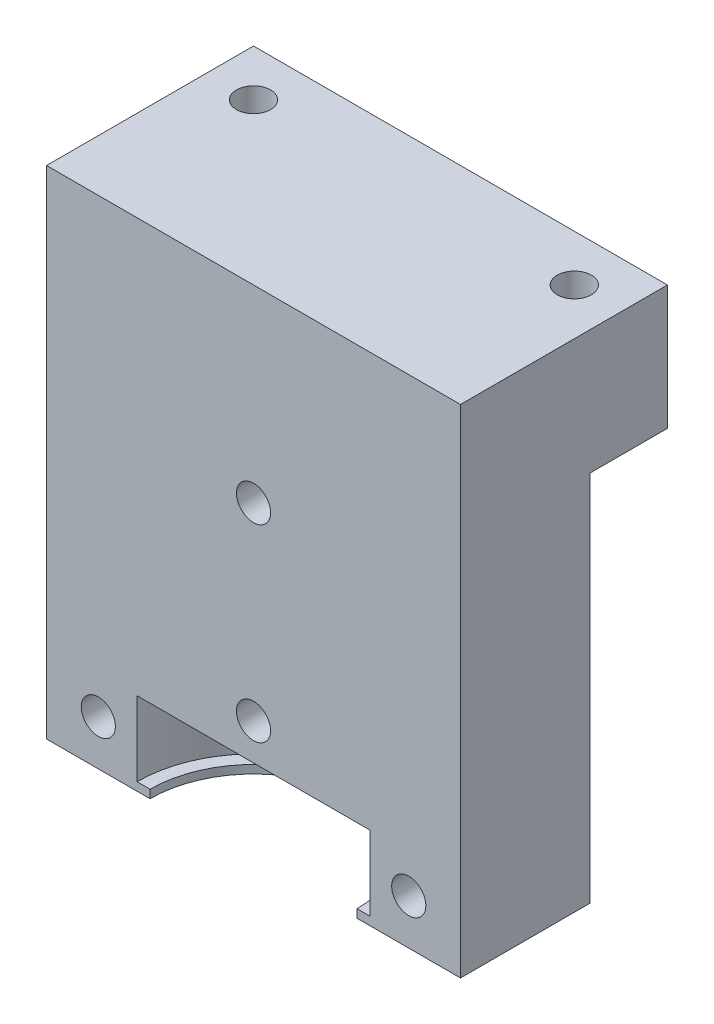
SolidWorks part; units mm, degrees
ref_plane "Front Plane" through (0, 0, 0) normal (0, 0, 1) x (1, 0, 0)
ref_plane "Top Plane" through (0, 0, 0) normal (0, 1, 0) x (1, 0, 0)
ref_plane "Right Plane" through (0, 0, 0) normal (1, 0, 0) x (0, 0, -1)
sketch "Sketch1" plane through (0, 0, 0) normal (0, 1, 0) x (1, 0, 0)
  line L1 (20, 20) -> (-20, 20)
  line L2 (20, 20) -> (20, -20)
  line L3 (20, -20) -> (-20, -20)
  line L4 (-20, 20) -> (-20, -20)
  line L5 (0, -20) -> (0, 20) construction
  line L6 (20, 0) -> (-20, 0) construction
  point P0 (0, 0)
extrude "Boss-Extrude1" add sketch "Sketch1" against normal blind 48
hole_wizard "M4x0.7 Tapped Hole1" positions "Sketch2" profile "Sketch3" tap size "M4x0.7" standard "ANSI Metric" end condition through all
sketch "Sketch2" plane through (0, 0, 0) normal (0, 1, 0) x (1, 0, 0)
  line L1 (-15.5, -15.5) -> (15.5, -15.5)
  line L2 (-15.5, -15.5) -> (-15.5, 15.5)
  line L3 (-15.5, 15.5) -> (15.5, 15.5)
  line L4 (15.5, -15.5) -> (15.5, 15.5)
  line L5 (15.5, 0) -> (0, 0) construction
  line L6 (0, 0) -> (0, -15.5) construction
  point P2 (-15.5, 15.5)
  point P4 (15.5, 15.5)
  point P6 (15.5, -15.5)
  point P8 (-15.5, -15.5)
  point P130 (-15.5, 15.5)
  point P131 (15.5, -15.5)
  point P132 (0, 0)
  dimension "D1" = 31
  dimension "D2" = 31
sketch "Sketch3" plane through (-15.5, 0, -15.5) normal (1, 0, 0) x (0, 0, 1)
  line L0 (0, 0) -> (0, 48)
  line L1 (0, 48) -> (1.65, 48)
  line L2 (1.65, 48) -> (1.65, 0)
  line L5 (1.65, 0) -> (0, 0)
  line L11 (0, -6.35) -> (0, 107.95) construction
  dimension "Thread Major Dia." = 3.3
  dimension "Thru Tap Drill Depth" = 48
sketch "Sketch10" plane through (0, 0, 0) normal (0, 1, 0) x (1, 0, 0)
  line L0 (20, -20) -> (20, 20) construction
  line L1 (-20, -20) -> (20, -20)
  line L2 (-20, -20) -> (-20, 0)
  line L3 (-20, 0) -> (20, 0)
  line L4 (20, -20) -> (20, 0)
extrude "Cut-Extrude4" cut sketch "Sketch10" against normal through all
sketch "Sketch11" plane through (0, 0, 0) normal (0, 0, 1) x (1, 0, 0)
  line L0 (0, 0) -> (0, -40) construction
  line L1 (0, -40) -> (11.25, -40)
  line L2 (0, -40) -> (0, -47.2)
  line L3 (0, -47.2) -> (11.25, -47.2)
  line L4 (11.25, -40) -> (11.25, -47.2)
  line L5 (20, 0) -> (-20, 0) construction
  dimension "D1" = 40
  dimension "D2" = 7.2
  dimension "D3" = 22.5
revolve "Cut-Revolve2" cut sketch "Sketch11" angle 360 about L0
sketch "Sketch12" plane through (0, -48, 0) normal (0, -1, 0) x (1, 0, 0)
  line L0 (20, 0) -> (-20, 0) construction
  circle A0 centre (0, 0) radius 10
  dimension "D1" = 20
extrude "Cut-Extrude5" cut sketch "Sketch12" against normal up to next
hole_wizard "M4x0.7 Tapped Hole2" positions "Sketch13" profile "Sketch14" tap size "M4x0.7" standard "ANSI Metric" end condition through all
sketch "Sketch13" plane through (0, 0, -20) normal (0, 0, -1) x (-1, 0, 0)
  line L0 (-15, -43.6281) -> (15, -43.6281) construction
  line L3 (0, -43.6281) -> (0, -36.4844) construction
  line L4 (0, -36.4844) -> (0, -18.2422) construction
  line L5 (0, -18.2422) -> (0, 0) construction
  line L8 (10, -47.2) -> (-10, -47.2) construction
  point P8 (15, -43.6281)
  point P10 (-15, -43.6281)
  point P12 (0, -36.4844)
  point P14 (0, -18.2422)
  point P33 (0, 0)
  dimension "D1" = 30
  dimension "D2" = 3.5719
  dimension "D3" = 7.1437
sketch "Sketch14" plane through (-15, -43.6281, -20) normal (1, 0, 0) x (0, 1, 0)
  line L0 (0, 0) -> (0, 20)
  line L1 (0, 20) -> (1.65, 20)
  line L2 (1.65, 20) -> (1.65, 0)
  line L5 (1.65, 0) -> (0, 0)
  line L11 (0, -6.35) -> (0, 107.95) construction
  dimension "Thru Tap Drill Dia." = 3.3
  dimension "Thru Tap Drill Depth" = 20
cosmetic thread "Hole Thread1" parameters "D2"=4
cosmetic thread "Hole Thread2" parameters "D2"=4
cosmetic thread "Hole Thread3" parameters "D2"=4
cosmetic thread "Hole Thread4" parameters "D2"=4
sketch "Sketch15" plane through (0, -48, 0) normal (0, -1, 0) x (1, 0, 0)
  line L1 (-20, -12.5) -> (20, -12.5)
  line L2 (-20, -12.5) -> (-20, -20)
  line L3 (-20, -20) -> (20, -20)
  line L4 (20, -12.5) -> (20, -20)
  line L5 (-20, -20) -> (-20, 0) construction
  point P4 (-20, -12.6534)
  point P7 (0, 0)
  dimension "D1" = 7.5
extrude "Cut-Extrude6" cut sketch "Sketch15" against normal blind 36
